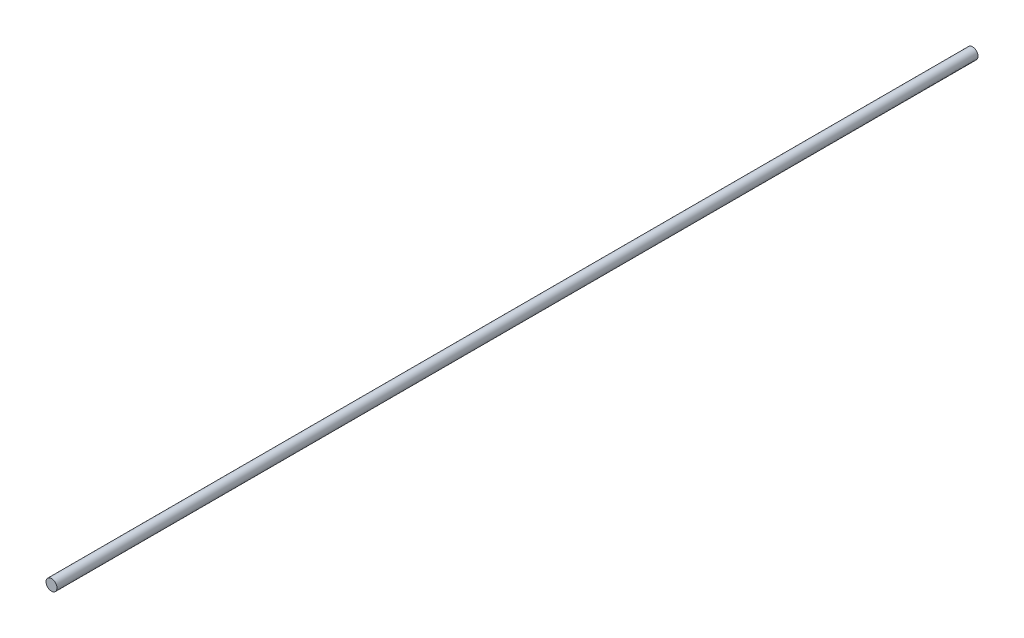
SolidWorks part; units mm, degrees
material "7075-T6 (SN)"
ref_plane "Front Plane" through (0, 0, 0) normal (0, 0, 1) x (1, 0, 0)
ref_plane "Top Plane" through (0, 0, 0) normal (0, 1, 0) x (1, 0, 0)
ref_plane "Right Plane" through (0, 0, 0) normal (1, 0, 0) x (0, 0, -1)
sketch "Sketch1" plane through (0, 0, 0) normal (0, 0, 1) x (1, 0, 0)
  circle A0 centre (0, 0) radius 1.8161
  dimension "D1" = 3.6322
extrude "Boss-Extrude1" add sketch "Sketch1" along normal blind 304.8
ref_plane "Plane1" through (0, 0, 152.4) normal (0, 0, 1) x (1, 0, 0)
sketch "Sketch2" plane through (0, 0, 152.4) normal (0, 0, 1) x (1, 0, 0)
  point P3 (0, 1.8161)
